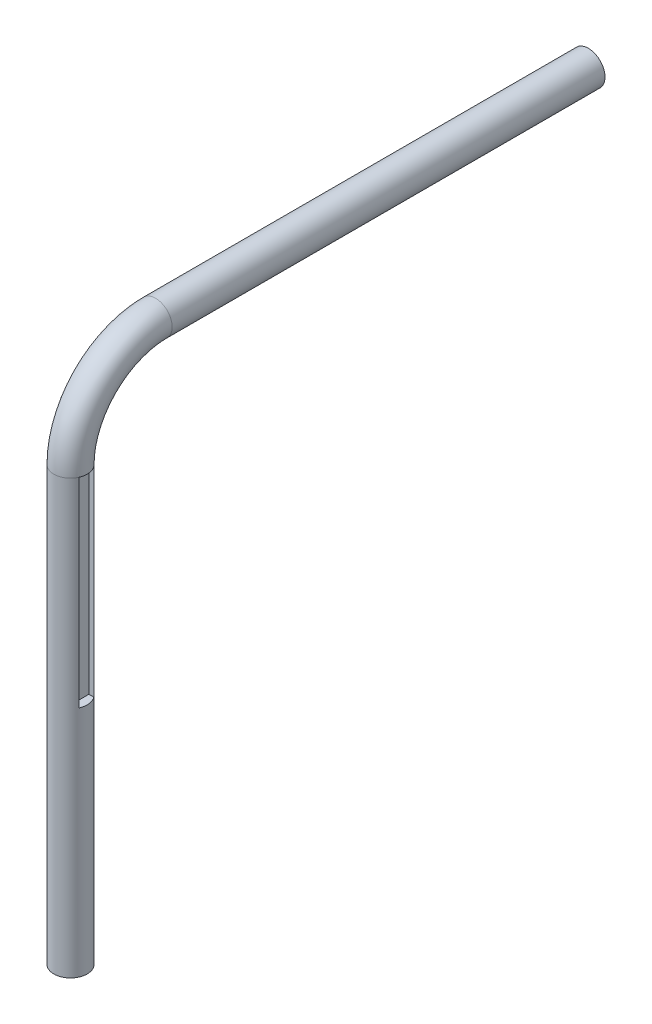
SolidWorks part; units mm, degrees
material "Cast Carbon Steel"
ref_plane "Front Plane" through (0, 0, 0) normal (0, 0, 1) x (1, 0, 0)
ref_plane "Top Plane" through (0, 0, 0) normal (0, 1, 0) x (1, 0, 0)
ref_plane "Right Plane" through (0, 0, 0) normal (1, 0, 0) x (0, 0, -1)
sketch "Sketch2" plane through (0, 0, 0) normal (1, 0, 0) x (0, 0, -1)
  arc A0 (-64.8338, 0) -> (0, 64.8338) centre (0, 0) cw
sketch "Sketch3" plane through (0, 0, 0) normal (0, 1, 0) x (1, 0, 0)
  circle A0 centre (0, -64.8338) radius 12.7
  circle A1 centre (0, -64.8338) radius 4.7625
  dimension "D1" = 25.4
  dimension "D2" = 7.9375
sweep "Sweep1" add profiles "Sketch3" path "Sketch2"
ref_plane "Plane1" through (0, 0, 0) normal (0, -1, 0) x (-1, 0, 0)
ref_plane "Plane2" through (0, 0, 0) normal (0, 0, -1) x (-1, 0, 0)
sketch "Sketch4" plane through (0, 0, 0) normal (0, -1, 0) x (-1, 0, 0)
  circle A0 centre (0, -64.8338) radius 12.7
  circle A1 centre (0, -64.8338) radius 4.7625
  dimension "D1" = 7.9375
  dimension "D2" = 25.4
extrude "Boss-Extrude3" add sketch "Sketch4" along normal blind 330.2
sketch "Sketch5" plane through (0, 0, 0) normal (0, 0, -1) x (-1, 0, 0)
  circle A0 centre (0, 64.8338) radius 12.7
  circle A1 centre (0, 64.8338) radius 4.7625
  dimension "D1" = 7.9375
  dimension "D2" = 25.4
extrude "Boss-Extrude4" add sketch "Sketch5" along normal blind 330.2
ref_plane "Plane3" through (-12.7, 0, 0) normal (-1, 0, 0) x (0, 0, 1)
ref_plane "Plane4" through (12.7, 0, 0) normal (1, 0, 0) x (0, 0, -1)
sketch "Sketch7" plane through (12.7, 0, 0) normal (1, 0, 0) x (0, 0, -1)
  line L0 (0, -13.97) -> (0, 13.97) construction
  line L1 (-69.85, 0) -> (-57.15, 0)
  line L2 (-69.85, 0) -> (-69.85, -152.4)
  line L3 (-69.85, -152.4) -> (-57.15, -152.4)
  line L4 (-57.15, 0) -> (-57.15, -152.4)
  line L5 (-52.1338, 0) -> (-77.5338, 0) construction
  point P9 (-63.5, -152.4)
  dimension "D1" = 12.7
  dimension "D2" = 152.4
  dimension "D3" = 57.15
  dimension "D4" = 63.5
extrude "Cut-Extrude2" cut sketch "Sketch7" against normal blind 6.35
